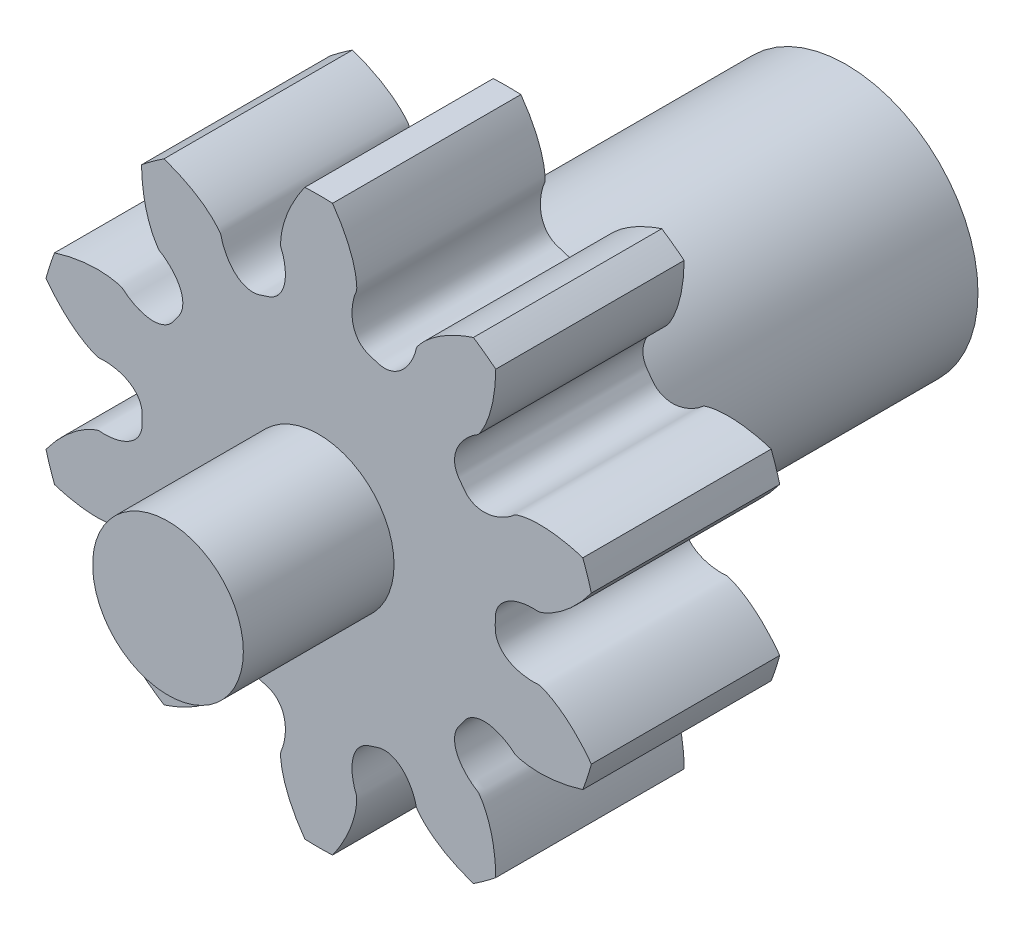
SolidWorks part; units mm, degrees
ref_plane "Front Plane" through (0, 0, 0) normal (0, 0, 1) x (1, 0, 0)
ref_plane "Top Plane" through (0, 0, 0) normal (0, 1, 0) x (1, 0, 0)
ref_plane "Right Plane" through (0, 0, 0) normal (1, 0, 0) x (0, 0, -1)
ref_axis "Axis1" through (0, 0, 55) along (0, 0, -1)
sketch "SketchRevolveSpurPinion" plane through (0, 0, 0) normal (1, 0, 0) x (0, 0, -1)
  line L0 (0, 0) -> (1, 0) construction
  line L1 (-5, 0) -> (-5, 15)
  line L2 (-5, 15) -> (5, 15)
  line L3 (5, 15) -> (5, 0)
  line L4 (5, 0) -> (-5, 0)
  dimension "Side1" = 5
  dimension "OutsideRadius" = 15
  dimension "Side2" = 5
revolve "SpurPinion" add sketch "SketchRevolveSpurPinion" angle 360 about L0
sketch "SketchToothSpurPinion" plane through (0, 0, 0) normal (0, 0, 1) x (1, 0, 0)
  arc A0 (14.5696, 4.0612) -> (14.5696, -4.0612) centre (0, 0) cw
  spline S0 degree 3 poles (14.5696, -4.0612) (14.4279, -3.8616) (14.2097, -3.578) (13.9044, -3.2288) (13.685, -2.9973) (13.4702, -2.7885) (13.2616, -2.6014) (13.0604, -2.4352) (12.8681, -2.289) (12.6858, -2.1617) (12.5149, -2.0524) (12.3563, -1.9598) (12.2112, -1.8827) (12.0805, -1.8201) (11.9652, -1.7699) (11.8428, -1.7244) (11.6492, -1.6493) (11.4346, -1.6969) (11.2391, -1.6839) (11.1188, -1.6757) (11.0016, -1.6626) (10.8872, -1.6459) (10.7757, -1.6253) (10.6672, -1.6008) (10.5615, -1.5723) (10.4588, -1.5399) (10.3591, -1.5035) (10.2623, -1.4628) (10.1684, -1.4177) (10.0776, -1.368) (9.9899, -1.3135) (9.9055, -1.2537) (9.8246, -1.1883) (9.7476, -1.1169) (9.675, -1.0391) (9.6075, -0.9545) (9.5461, -0.8628) (9.4917, -0.7639) (9.4458, -0.658) (9.4098, -0.5457) (9.3848, -0.4282) (9.3744, -0.3207) (9.3704, -0.1777) (9.3783, 0) (9.3704, 0.1777) (9.3744, 0.3207) (9.3848, 0.4282) (9.4098, 0.5457) (9.4458, 0.658) (9.4917, 0.7639) (9.5461, 0.8628) (9.6075, 0.9545) (9.675, 1.0391) (9.7476, 1.1169) (9.8246, 1.1883) (9.9055, 1.2537) (9.9899, 1.3135) (10.0776, 1.368) (10.1684, 1.4177) (10.2623, 1.4628) (10.3591, 1.5035) (10.4588, 1.5399) (10.5615, 1.5723) (10.6672, 1.6008) (10.7757, 1.6253) (10.8872, 1.6459) (11.0016, 1.6626) (11.1188, 1.6757) (11.2391, 1.6839) (11.4346, 1.6969) (11.6492, 1.6493) (11.8428, 1.7244) (11.9652, 1.7699) (12.0805, 1.8201) (12.2112, 1.8827) (12.3563, 1.9598) (12.5149, 2.0524) (12.6858, 2.1617) (12.8681, 2.289) (13.0604, 2.4352) (13.2616, 2.6014) (13.4702, 2.7885) (13.685, 2.9973) (13.9044, 3.2288) (14.2097, 3.578) (14.4279, 3.8616) (14.5696, 4.0612) knots 0 0 0 0 0.05171 0.075524 0.097977 0.119069 0.138801 0.157172 0.174182 0.189831 0.204119 0.217047 0.228613 0.238819 0.247664 0.255149 0.266491 0.290789 0.299455 0.307937 0.316241 0.324377 0.332355 0.340185 0.347882 0.355458 0.36293 0.370317 0.377638 0.384917 0.392177 0.399447 0.406755 0.414132 0.42161 0.429216 0.436977 0.444911 0.453028 0.461323 0.469778 0.478358 0.484106 0.5 0.515894 0.521642 0.530222 0.538677 0.546972 0.555089 0.563023 0.570784 0.57839 0.585868 0.593245 0.600553 0.607823 0.615083 0.622362 0.629683 0.63707 0.644542 0.652118 0.659815 0.667645 0.675623 0.683759 0.692063 0.700545 0.709211 0.733509 0.744851 0.752336 0.761181 0.771387 0.782953 0.795881 0.810169 0.825818 0.842828 0.861199 0.880931 0.902023 0.924476 0.94829 1 1 1 1
extrude "ToothExtrudeCutSpurPinion" cut sketch "SketchToothSpurPinion" against normal blind 5 and the other way blind 5
pattern_circular "PatternSpurPinion" count 10 over 360 about axis through (0, 0, 55) along (0, 0, -1) of "ToothExtrudeCutSpurPinion"
sketch "BoreRevolveSketch" plane through (0, 0, 0) normal (1, 0, 0) x (0, 0, -1)
  line L0 (0, 0) -> (1, 0) construction
sketch "AuxiliarySketchSpurPinion" plane through (0, 0, 0) normal (0, 0, 1) x (1, 0, 0)
  circle A0 centre (0, 0) radius 12.5 construction
  circle A1 centre (0, 0) radius 11.7462 construction
  circle A2 centre (0, 0) radius 12.2336 construction
  circle A3 centre (0, 0) radius 15 construction
  circle A4 centre (0, 0) radius 9.375 construction
  dimension "PitchDiameter" = 25
  dimension "BaseDiameter" = 23.4923
  dimension "FormDiameter" = 24.4671
  dimension "MajorDiameter" = 30
  dimension "MinorDiameter" = 18.75
sketch "Sketch3" plane through (0, 0, 5) normal (0, 0, 1) x (1, 0, 0)
  circle A0 centre (0, 0) radius 4
extrude "Boss-Extrude1" add sketch "Sketch3" along normal blind 8
sketch "Sketch4" plane through (0, 0, -5) normal (0, 0, -1) x (-1, 0, 0)
  circle A2 centre (0, 0) radius 7
extrude "Boss-Extrude2" add sketch "Sketch4" along normal blind 18
sketch "Sketch6" plane through (0, 0, -23) normal (0, 0, -1) x (-1, 0, 0)
  line L8 (2.7568, -3.3) -> (-2.7568, -3.3)
  arc A0 (-2.7568, -3.3) -> (2.7568, -3.3) centre (0, 0) cw
extrude "Cut-Extrude1" cut sketch "Sketch6" against normal blind 15
